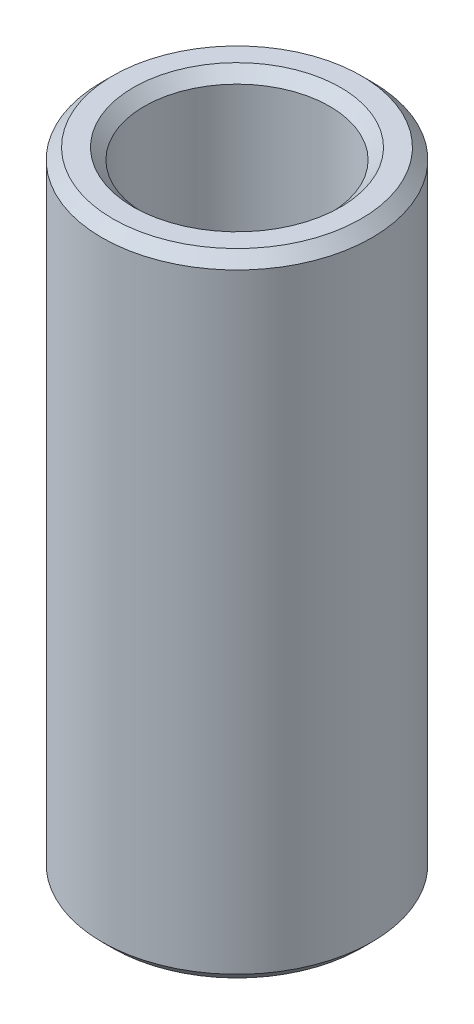
SolidWorks part; units mm, degrees
ref_plane "Front Plane" through (0, 0, 0) normal (0, 0, 1) x (1, 0, 0)
ref_plane "Top Plane" through (0, 0, 0) normal (0, 1, 0) x (1, 0, 0)
ref_plane "Right Plane" through (0, 0, 0) normal (1, 0, 0) x (0, 0, -1)
sketch "Sketch1" plane through (0, 0, 0) normal (0, 1, 0) x (1, 0, 0)
  circle A0 centre (0, 0) radius 45
  dimension "SLEEVE_OD" = 90
extrude "Boss-Extrude1" add sketch "Sketch1" along normal blind 210.6121
sketch "Sketch2" plane through (0, 0, 0) normal (0, 1, 0) x (1, 0, 0)
  circle A0 centre (0, 0) radius 30.9146
  dimension "BORE_D" = 61.8292
extrude "Cut-Extrude1" cut sketch "Sketch2" along normal through all
chamfer "Chamfer1" distance 3.6311 angle 45 4 edges at (0, 210.6121, 30.9146) (0, 0, 30.9146) (0, 0, 45) (0, 210.6121, 45)
